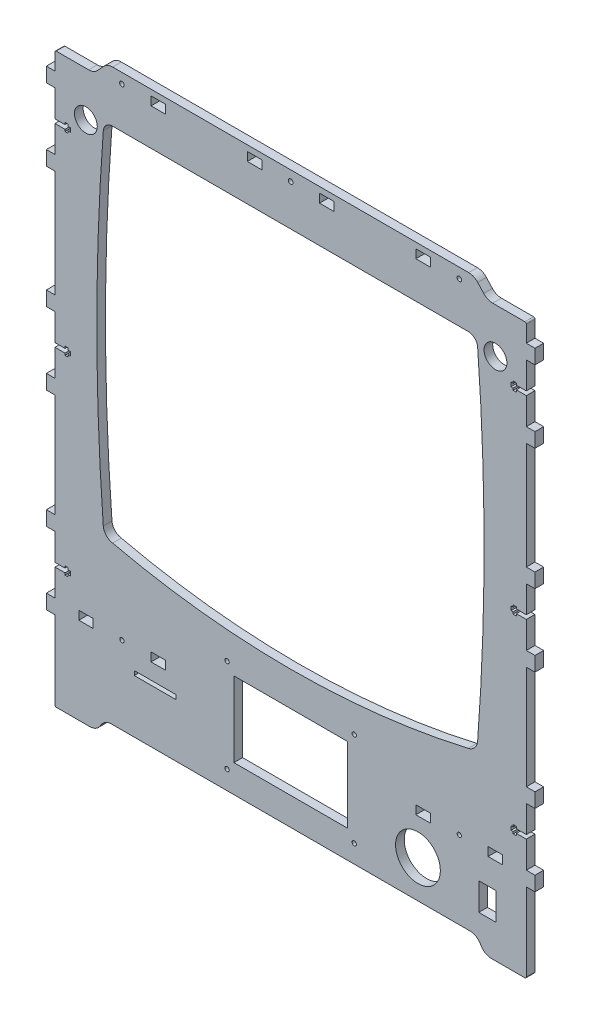
SolidWorks part; units mm, degrees
ref_plane "Спереди" through (0, 0, 0) normal (0, 0, 1) x (1, 0, 0)
ref_plane "Сверху" through (0, 0, 0) normal (0, 1, 0) x (1, 0, 0)
ref_plane "Справа" through (0, 0, 0) normal (1, 0, 0) x (0, 0, -1)
sketch "Эскиз1" plane through (0, 0, 0) normal (0, 0, 1) x (1, 0, 0)
  line L0 (-95.8892, 197.3491) -> (-85.8892, 197.3491)
  line L1 (-85.8892, 197.3491) -> (-85.8892, 191.3491)
  line L2 (-85.8892, 191.3491) -> (-95.8892, 191.3491)
  line L3 (-95.8892, 191.3491) -> (-95.8892, 197.3491)
  line L4 (97.3908, 191.3491) -> (87.3908, 191.3491)
  line L5 (87.3908, 191.3491) -> (87.3908, 197.3491)
  line L6 (87.3908, 197.3491) -> (97.3908, 197.3491)
  line L7 (97.3908, 197.3491) -> (97.3908, 191.3491)
  line L8 (97.3654, -141.9477) -> (87.3654, -141.9477)
  line L9 (87.3654, -141.9477) -> (87.3654, -135.9477)
  line L10 (87.3654, -135.9477) -> (97.3654, -135.9477)
  line L11 (97.3654, -135.9477) -> (97.3654, -141.9477)
  line L12 (147.3854, -141.9477) -> (137.3854, -141.9477)
  line L13 (137.3854, -141.9477) -> (137.3854, -135.9477)
  line L14 (137.3854, -135.9477) -> (147.3854, -135.9477)
  line L15 (147.3854, -135.9477) -> (147.3854, -141.9477)
  line L16 (-135.8946, -141.9477) -> (-145.8946, -141.9477)
  line L17 (-145.8946, -141.9477) -> (-145.8946, -135.9477)
  line L18 (-145.8946, -135.9477) -> (-135.8946, -135.9477)
  line L19 (-135.8946, -135.9477) -> (-135.8946, -141.9477)
  line L20 (-85.8746, -141.9477) -> (-95.8746, -141.9477)
  line L21 (-95.8746, -141.9477) -> (-95.8746, -135.9477)
  line L22 (-95.8746, -135.9477) -> (-85.8746, -135.9477)
  line L23 (-85.8746, -135.9477) -> (-85.8746, -141.9477)
  line L24 (-19.2392, 191.3491) -> (-29.2392, 191.3491)
  line L25 (-29.2392, 191.3491) -> (-29.2392, 197.3491)
  line L26 (-29.2392, 197.3491) -> (-19.2392, 197.3491)
  line L27 (-19.2392, 197.3491) -> (-19.2392, 191.3491)
  line L28 (30.7408, 191.3491) -> (20.7408, 191.3491)
  line L29 (20.7408, 191.3491) -> (20.7408, 197.3491)
  line L30 (20.7408, 197.3491) -> (30.7408, 197.3491)
  line L31 (30.7408, 197.3491) -> (30.7408, 191.3491)
  line L32 (-122.3991, 165.873) -> (123.6241, 165.873)
  line L33 (40.0454, -173.6357) -> (40.0454, -121.6361)
  line L34 (40.0454, -121.6361) -> (-38.5546, -121.6361)
  line L35 (-38.5546, -121.6361) -> (-38.5546, -173.6357)
  line L36 (-38.5546, -173.6357) -> (40.0454, -173.6357)
  line L37 (142.9388, -159.6762) -> (142.9388, -178.6762)
  line L38 (142.9388, -178.6762) -> (130.9388, -178.6762)
  line L39 (130.9388, -178.6762) -> (130.9388, -159.6762)
  line L40 (130.9388, -159.6762) -> (142.9388, -159.6762)
  line L41 (-162.3492, -146.9309) -> (-168.3546, -146.9309)
  line L42 (-168.3546, -146.9309) -> (-168.3546, -136.9309)
  line L43 (-168.3546, -136.9309) -> (-162.3546, -136.9309)
  line L44 (-162.3546, -136.9309) -> (-162.3546, -118.3209)
  line L45 (-162.3546, -96.9409) -> (-168.3546, -96.9409)
  line L46 (-168.3546, -96.9409) -> (-168.3546, -86.9409)
  line L47 (-168.3546, -86.9409) -> (-162.3546, -86.9409)
  line L48 (-162.3546, -86.9409) -> (-162.3546, -15.2109)
  line L49 (-162.3546, -15.2109) -> (-168.3546, -15.2109)
  line L50 (-162.3546, 34.7891) -> (-168.3546, 34.7891)
  line L51 (-168.3546, -5.2109) -> (-162.3546, -5.2109)
  line L52 (-168.3546, 44.7891) -> (-162.3546, 44.7891)
  line L56 (-162.3546, 128.9491) -> (-162.3546, 147.5491)
  line L57 (-162.3492, 168.9491) -> (-168.3492, 168.9491)
  line L58 (-168.3492, 168.9491) -> (-168.3492, 178.9491)
  line L59 (-168.3492, 178.9491) -> (-162.3492, 178.9491)
  line L60 (-162.3492, 178.9491) -> (-162.3492, 190.3491)
  line L61 (-162.3492, -200.9709) -> (-162.3492, -146.9309)
  line L62 (163.8454, -146.9309) -> (169.8454, -146.9309)
  line L63 (169.8454, -146.9309) -> (169.8454, -136.9309)
  line L64 (169.8454, -136.9309) -> (163.8513, -136.9309)
  line L65 (163.8513, -136.9309) -> (163.8513, -118.3209)
  line L66 (163.9392, -96.9409) -> (169.8512, -96.9409)
  line L67 (169.8512, -96.9409) -> (169.8512, -86.9409)
  line L68 (169.8512, -86.9409) -> (163.8512, -86.9409)
  line L69 (163.8512, -86.9409) -> (163.8512, -15.2109)
  line L70 (163.8512, -15.2109) -> (169.8512, -15.2109)
  line L71 (163.8512, 34.7891) -> (169.8512, 34.7891)
  line L72 (169.8512, -5.2109) -> (163.8512, -5.2109)
  line L73 (169.8512, 44.7891) -> (163.8512, 44.7891)
  line L74 (163.8512, 118.9491) -> (169.8512, 118.9491)
  line L75 (169.8512, 118.9491) -> (169.8512, 128.9491)
  line L76 (169.8512, 128.9491) -> (163.8512, 128.9491)
  line L77 (163.8512, 128.9491) -> (163.8512, 147.5491)
  line L78 (163.8508, 168.9491) -> (169.8508, 168.9491)
  line L79 (169.8508, 168.9491) -> (169.8508, 178.9491)
  line L80 (169.8508, 178.9491) -> (163.8508, 178.9491)
  line L81 (163.8508, 178.9491) -> (163.8508, 190.3491)
  line L82 (156.9388, 150.3491) -> (156.9388, 151.7492)
  line L83 (163.9392, -115.5209) -> (156.9392, -115.5209)
  line L84 (156.9392, -114.1224) -> (154.7382, -114.1224)
  line L85 (156.9399, -118.3209) -> (163.8513, -118.3209)
  line L86 (153.2384, -118.3222) -> (154.7405, -118.3222)
  line L87 (-155.4441, 11.989) -> (-153.2432, 11.989)
  line L88 (154.7382, -114.1224) -> (154.7382, -115.5222)
  line L89 (154.7391, 16.1893) -> (153.24, 16.1893)
  line L90 (153.2384, -115.5222) -> (153.2384, -118.3222)
  line L91 (-155.4426, -119.721) -> (-153.2418, -119.721)
  line L92 (163.8508, 150.3491) -> (156.9388, 150.3491)
  line L93 (156.9399, -119.7231) -> (156.9399, -118.3209)
  line L94 (156.9392, -115.5209) -> (156.9392, -114.1224)
  line L95 (154.7382, -115.5222) -> (153.2384, -115.5222)
  line L96 (154.741, 147.5502) -> (154.741, 146.1493)
  line L97 (-155.4451, -114.1209) -> (-155.4451, -115.5209)
  line L98 (154.7415, 13.3902) -> (154.7415, 11.9893)
  line L99 (-162.3546, 147.5491) -> (-155.4441, 147.5491)
  line L100 (-155.4441, 147.5491) -> (-155.4441, 146.149)
  line L101 (-155.4398, 150.3491) -> (-162.3492, 150.3491)
  line L102 (-153.2398, 150.3482) -> (-153.2398, 151.7491)
  line L103 (154.7405, -118.3222) -> (154.7405, -119.7231)
  line L104 (-155.4451, -115.5209) -> (-162.3546, -115.5209)
  line L105 (154.741, 151.7492) -> (154.741, 150.3493)
  line L106 (156.9417, 146.1493) -> (156.9417, 147.5491)
  line L107 (-153.2432, 13.3622) -> (-151.7428, 13.3622)
  line L108 (-155.4426, -118.3209) -> (-155.4426, -119.721)
  line L109 (153.241, 150.3493) -> (153.241, 147.5502)
  line L110 (-153.2451, 17.5891) -> (-155.4451, 17.5891)
  line L111 (-162.3546, 13.3891) -> (-155.4441, 13.3891)
  line L112 (154.741, 146.1493) -> (156.9417, 146.1493)
  line L113 (153.241, 147.5502) -> (154.741, 147.5502)
  line L114 (-153.2433, 147.5489) -> (-151.7375, 147.5489)
  line L115 (-151.7428, 13.3622) -> (-151.7428, 16.1885)
  line L116 (163.8512, 16.1891) -> (156.9392, 16.1891)
  line L117 (154.7391, 17.5621) -> (154.7391, 16.1893)
  line L118 (154.741, 150.3493) -> (153.241, 150.3493)
  line L119 (154.7415, 11.9893) -> (156.9417, 11.9893)
  line L120 (-153.2451, -114.1209) -> (-155.4451, -114.1209)
  line L121 (-151.7436, -118.3211) -> (-151.7436, -115.5218)
  line L122 (-153.2418, -118.3211) -> (-151.7436, -118.3211)
  line L123 (-153.2432, 11.989) -> (-153.2432, 13.3622)
  line L124 (156.9417, 13.3891) -> (163.8512, 13.3891)
  line L125 (-162.3546, -118.3209) -> (-155.4426, -118.3209)
  line L126 (153.24, 16.1893) -> (153.24, 13.3902)
  line L127 (-153.2451, -115.5218) -> (-153.2451, -114.1209)
  line L128 (-151.7428, 16.1885) -> (-153.2451, 16.1885)
  line L129 (-155.4441, 146.149) -> (-153.2433, 146.149)
  line L130 (-153.2418, -119.721) -> (-153.2418, -118.3211)
  line L131 (-155.4398, 151.7491) -> (-155.4398, 150.3491)
  line L132 (-151.7436, -115.5218) -> (-153.2451, -115.5218)
  line L133 (-153.2433, 146.149) -> (-153.2433, 147.5489)
  line L134 (153.24, 13.3902) -> (154.7415, 13.3902)
  line L135 (156.9388, 151.7492) -> (154.741, 151.7492)
  line L136 (-151.7375, 147.5489) -> (-151.738, 150.3482)
  line L137 (156.9417, 147.5491) -> (163.8512, 147.5491)
  line L138 (-155.4451, 16.1891) -> (-162.3546, 16.1891)
  line L139 (156.9417, 11.9893) -> (156.9417, 13.3891)
  line L140 (-155.4451, 17.5891) -> (-155.4451, 16.1891)
  line L141 (154.7405, -119.7231) -> (156.9399, -119.7231)
  line L142 (-153.2398, 151.7491) -> (-155.4398, 151.7491)
  line L143 (156.9392, 17.5621) -> (154.7391, 17.5621)
  line L144 (-151.738, 150.3482) -> (-153.2398, 150.3482)
  line L145 (-162.3546, -115.5209) -> (-162.3546, -96.9409)
  line L146 (-162.3492, 150.3491) -> (-162.3492, 168.9491)
  line L147 (163.9392, -115.5209) -> (163.9392, -96.9409)
  line L148 (163.8508, 150.3491) -> (163.8508, 168.9491)
  line L149 (-139.0924, 191.3491) -> (-161.5253, 191.3491)
  line L150 (-128.7242, 198.5879) -> (-132.8221, 194.1104)
  line L151 (123.9554, 201.3491) -> (-122.4539, 201.3491)
  line L152 (130.2257, 198.5879) -> (134.3236, 194.1104)
  line L153 (140.5939, 191.3491) -> (162.8508, 191.3491)
  line L154 (-131.8015, -198.9146) -> (-129.7448, -195.8949)
  line L155 (162.7628, -201.9477) -> (139.7264, -201.9477)
  line L156 (133.303, -198.9146) -> (131.2463, -195.8949)
  line L157 (-161.4373, -201.9509) -> (-138.3129, -201.9509)
  line L158 (-123.2334, -192.8586) -> (124.7349, -192.8586)
  line L159 (163.8454, -200.9731) -> (163.8454, -146.9309)
  line L160 (-162.3546, 13.3891) -> (-162.3546, -5.2109)
  line L161 (-168.3546, -15.2109) -> (-168.3546, -5.2109)
  line L162 (-168.3546, 34.7891) -> (-168.3546, 44.7891)
  line L163 (-162.3546, 44.7891) -> (-162.3546, 118.9491)
  line L164 (163.8512, 13.3891) -> (163.8512, -5.2109)
  line L165 (169.8512, -15.2109) -> (169.8512, -5.2109)
  line L166 (169.8512, 34.7891) -> (169.8512, 44.7891)
  line L167 (163.8512, 44.7891) -> (163.8512, 118.9491)
  line L168 (-155.4441, 13.3891) -> (-155.4441, 11.989)
  line L169 (-153.2451, 16.1885) -> (-153.2451, 17.5891)
  line L170 (156.9392, 16.1891) -> (156.9392, 17.5621)
  line L171 (-162.3546, 34.7891) -> (-162.3546, 16.1891)
  line L172 (163.8512, 34.7891) -> (163.8512, 16.1891)
  line L173 (-107.5042, -155.9271) -> (-107.5042, -152.9271)
  line L174 (-107.5042, -152.9271) -> (-78.5042, -152.9271)
  line L175 (-78.5042, -152.9271) -> (-78.5042, -155.9271)
  line L176 (-78.5042, -155.9271) -> (-107.5042, -155.9271)
  line L177 (-162.3546, 128.9491) -> (-168.3546, 128.9491)
  line L178 (-162.3546, 118.9491) -> (-168.3546, 118.9491)
  line L179 (-168.3546, 118.9491) -> (-168.3546, 128.9491)
  line L180 (-155.4426, -141.9477) -> (156.9399, -141.9477) construction
  arc A0 (-122.4711, -84.0153) -> (123.6489, -84.0153) centre (0.5889, 449.8336) ccw
  arc A1 (-128.9341, 159.8968) -> (-128.9472, -76.974) centre (1428.6282, 41.3753) ccw
  arc A2 (130.1254, -76.9742) -> (130.1588, 159.8968) centre (-1430.5029, 41.6814) ccw
  circle A3 centre (44.7454, -115.1361) radius 1.5
  circle A4 centre (44.7454, -180.3857) radius 1.5
  circle A5 centre (-43.2546, -179.8825) radius 1.5
  circle A6 centre (-43.2546, -115.1361) radius 1.5
  circle A7 centre (88.8454, -166.9477) radius 15.5
  arc A8 (130.1588, 159.8968) -> (123.6241, 165.873) centre (123.6241, 159.3123) ccw
  arc A9 (-122.3991, 165.873) -> (-128.9341, 159.8968) centre (-122.472, 159.3916) ccw
  arc A10 (-128.9472, -76.974) -> (-122.4711, -84.0153) centre (-121.245, -76.3888) ccw
  arc A11 (123.6489, -84.0153) -> (130.1254, -76.9742) centre (121.7477, -75.7674) ccw
  circle A12 centre (0.7508, 194.3491) radius 1.6
  circle A13 centre (-116.0492, 194.3491) radius 1.6
  arc A14 (134.3236, 194.1104) -> (140.5939, 191.3491) centre (140.5939, 199.8491) ccw
  arc A15 (-161.5253, 191.3491) -> (-162.3492, 190.3491) centre (-161.4373, 190.4372) ccw
  arc A16 (-139.0924, 191.3491) -> (-132.8221, 194.1104) centre (-139.0924, 199.8491) ccw
  arc A17 (-122.4539, 201.3491) -> (-128.7242, 198.5879) centre (-122.4539, 192.8491) ccw
  circle A18 centre (117.5508, 194.3491) radius 1.6
  arc A19 (130.2257, 198.5879) -> (123.9554, 201.3491) centre (123.9554, 192.8491) ccw
  arc A20 (163.8508, 190.3491) -> (162.8508, 191.3491) centre (162.8508, 190.3491) ccw
  arc A21 (-123.2334, -192.8586) -> (-129.7448, -195.8949) centre (-123.2334, -201.3586) ccw
  arc A22 (-138.3129, -201.9509) -> (-131.8015, -198.9146) centre (-138.3129, -193.4509) ccw
  arc A23 (131.2463, -195.8949) -> (124.7349, -192.8586) centre (124.7349, -201.3586) ccw
  arc A24 (133.303, -198.9146) -> (139.7264, -201.9477) centre (139.7677, -193.542) ccw
  arc A25 (-162.3492, -200.9709) -> (-161.4373, -201.9509) centre (-161.3926, -200.9949) ccw
  arc A26 (162.7628, -201.9477) -> (163.8454, -200.9731) centre (162.8028, -200.9035) ccw
  circle A27 centre (-140.9992, 160.3491) radius 7.9
  circle A28 centre (142.5008, 160.3491) radius 7.9
  circle A29 centre (-115.9946, -138.9477) radius 1.5
  circle A30 centre (117.4854, -138.9477) radius 1.5
  point P239 (87.3908, 194.3491)
  point P241 (-162.3492, 184.6491)
  dimension "D11" = 15.8
  dimension "D12" = 15.8
  dimension "D53" = 31
  dimension "D88" = 283.5
  dimension "D1" = 10
  dimension "D2" = 12.4
  dimension "D3" = 12.4
  dimension "D4" = 10
  dimension "D5" = 18.6
  dimension "D6" = 2.8
  dimension "D7" = 18.6
  dimension "D8" = 10
  dimension "D9" = 10
  dimension "D10" = 10
  dimension "D13" = 6
  dimension "D14" = 18.6
  dimension "D15" = 18.6
  dimension "D16" = 10
  dimension "D17" = 74.16
  dimension "D18" = 74.16
  dimension "D19" = 10
  dimension "D20" = 10
  dimension "D21" = 18.6
  dimension "D22" = 18.6
  dimension "D23" = 18.6
  dimension "D24" = 18.6
  dimension "D25" = 10
  dimension "D26" = 10
  dimension "D27" = 71.73
  dimension "D28" = 71.73
  dimension "D29" = 10
  dimension "D30" = 10
  dimension "D31" = 18.58
  dimension "D32" = 18.58
  dimension "D33" = 18.61
  dimension "D34" = 18.61
  dimension "D35" = 10
  dimension "D36" = 10
  dimension "D37" = 54.04
  dimension "D38" = 54.0422
  dimension "D39" = 403.2968
  dimension "D40" = 2.8
  dimension "D41" = 2.8
  dimension "D42" = 2.8
  dimension "D43" = 2.8
  dimension "D44" = 403.3
  dimension "D45" = 10
  dimension "D46" = 10
  dimension "D47" = 10
  dimension "D48" = 169.1
  dimension "D49" = 10
  dimension "D50" = 10
  dimension "D51" = 10
  dimension "D52" = 10
  dimension "D54" = 338.2
  dimension "D55" = 169.1
  dimension "D56" = 10
  dimension "D57" = 52.3
  dimension "D58" = 52.3
  dimension "D59" = 72.46
  dimension "D60" = 72.46
  dimension "D61" = 56.65
  dimension "D62" = 56.65
  dimension "D63" = 19.99
  dimension "D64" = 19.99
  dimension "D65" = 21.35
  dimension "D66" = 21.35
  dimension "D67" = 22.46
  dimension "D68" = 22.46
  dimension "D69" = 19.9
  dimension "D70" = 19.9
  dimension "D71" = 20.12
  dimension "D72" = 20.12
  dimension "D73" = 47.32
  dimension "D74" = 78.6
  dimension "D75" = 47.32
  dimension "D76" = 4.7
  dimension "D77" = 4.7
  dimension "D78" = 4.7
  dimension "D79" = 4.7
  dimension "D80" = 6.5
  dimension "D81" = 6.5
  dimension "D82" = 6
  dimension "D83" = 60
  dimension "D84" = 55.02
  dimension "D85" = 6
  dimension "D86" = 29
  dimension "D87" = 3
  dimension "D89" = 4
  dimension "D90" = 7
  dimension "D91" = 6
  dimension "D92" = 4
  dimension "D93" = 6
  dimension "D94" = 7
  dimension "D95" = 4
  dimension "D96" = 6
  dimension "D97" = 4
  dimension "D98" = 2.8
  dimension "D99" = 7
  dimension "D100" = 31
  dimension "D101" = 31
  dimension "D102" = 166.56
  dimension "D103" = 131.73
  dimension "D104" = 51.9996
  dimension "D105" = 6
  dimension "D106" = 3
  dimension "D107" = 6
  dimension "D108" = 3
  dimension "D109" = 6
  dimension "D110" = 25
  dimension "D111" = 6
  dimension "D112" = 75
  dimension "D114" = 326.2
extrude "Бобышка-Вытянуть2" add sketch "Эскиз1" along normal blind 6 contours A5 | A4 | A3 | A13 | A12 | A7 | A6 | L32 A8 A2 A11 A0 A10 A1 A9 | A18 | A30 | A29 | A28 | A27 | L4 L5 L6 L7 | L0 L1 L2 L3 | L20 L21 L22 L23 | L16 L17 L18 L19 | L12 L13 L14 L15 | L8 L9 L10 L11 | L37 L38 L39 L40 | L33 L34 L35 L36 | L28 L29 L30 L31 | L24 L25 L26 L27 | L41 L42 L43 L44 L125 L108 L91 L130 L122 L121 L132 L127 L120 L97 L104 L145 L45 L46 L47 L48 L49 L161 L51 L160 L111 L168 L87 L123 L107 L115 L128 L169 L110 L140 L138 L171 L50 L162 L52 L163 L178 L179 L177 L56 L99 L100 L129 L133 L114 L136 L144 L102 L142 L131 L101 L146 L57 L58 L59 L60 A15 L149 A16 L150 A17 L151 A19 L152 A14 L153 A20 L81 L80 L79 L78 L148 L92 L82 L135 L105 L118 L109 L113 L96 L112 L106 L137 L77 L76 L75 L74 L167 L73 L166 L71 L172 L116 L170 L143 L117 L89 L126 L134 L98 L119 L139 L124 L164 L72 L165 L70 L69 L68 L67 L66 L147 L83 L94 L84 L88 L95 L90 L86 L103 L141 L93 L85 L65 L64 L63 L62 L159 A26 L155 A24 L156 A23 L158 A21 L154 A22 L157 A25 L61 | L173 L174 L175 L176
